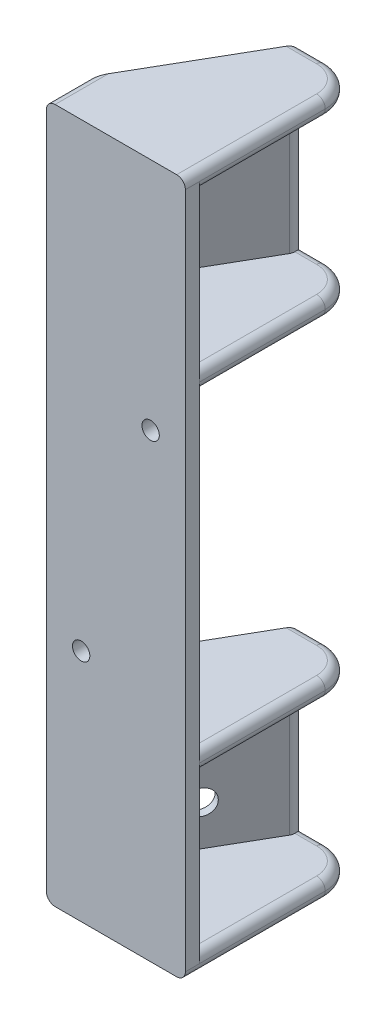
SolidWorks part; units mm, degrees
note: The reader was unsure of these and kept them because the rebuilt part matched: shared geometry of "Sketch2<2>".
material "ABS"
ref_plane "X-Y Datum" through (0, 0, 0) normal (0, 0, 1) x (1, 0, 0)
ref_plane "X-Z Datum" through (0, 0, 0) normal (0, 1, 0) x (1, 0, 0)
ref_plane "Y-Z Datum" through (0, 0, 0) normal (1, 0, 0) x (0, 0, -1)
sketch "Sketch1" plane through (0, 0, 0) normal (0, 1, 0) x (1, 0, 0)
  line L0 (0, 0) -> (-25.4, 0)
  line L1 (-25.4, 0) -> (-25.4, 6.985)
  line L2 (-25.4, 6.985) -> (0, 50.9791)
  line L3 (0, 50.9791) -> (0, 0)
  dimension "D1" = 25.4
  dimension "D2" = 60
  dimension "D3" = 6.985
extrude "Boss-Extrude1" add sketch "Sketch1" along normal blind 127
ref_plane "Plane1" through (0, 63.5, 0) normal (0, -1, 0) x (-1, 0, 0)
sketch "Sketch2" plane through (0, 63.5, 0) normal (0, -1, 0) x (-1, 0, 0)
  line L0 (0, 2.54) -> (23.8125, 2.54)
  line L1 (0, 0) -> (0, 50.9791) construction
  line L2 (23.8125, 2.54) -> (23.8125, 6.5596)
  line L3 (23.8125, 6.5596) -> (0, 47.8041)
  line L4 (0, 47.8041) -> (0, 2.54)
  line L5 (23.8125, 2.54) -> (23.8125, 0) construction
  line L6 (25.4, 0) -> (0, 0) construction
  line L7 (23.8125, 2.54) -> (25.4, 2.54) construction
  line L8 (25.4, 6.985) -> (25.4, 0) construction
  line L9 (25.4, 6.985) -> (24.0252, 6.1912) construction
  line L10 (0, 50.9791) -> (25.4, 6.985) construction
  dimension "D1" = 2.54
  dimension "D2" = 1.5875
extrude "Cut-Extrude1" cut sketch "Sketch2" against normal offset from surface (28.575 mm away) 3.175 from offset 31.75 up to face at (-12.7, 127, -14.491) offset against normal yes
extrude "Cut-Extrude2" cut sketch "Sketch2<2>" along normal offset from surface (28.575 mm away) 3.175 from offset 31.75 up to face at (-12.7, 0, -14.491)
sketch "Sketch2<2>" plane through (0, 63.5, 0) normal (0, -1, 0) x (-1, 0, 0) same geometry as "Sketch2"
sketch "Sketch3" plane through (0, 63.5, 0) normal (0, -1, 0) x (-1, 0, 0)
  line L0 (0, 0) -> (0, 50.9791) construction
  line L1 (25.4, 2.54) -> (0, 2.54)
  line L2 (25.4, 2.54) -> (25.4, 53.34)
  line L3 (25.4, 53.34) -> (0, 53.34)
  line L4 (0, 2.54) -> (0, 53.34)
  line L5 (25.4, 6.985) -> (25.4, 0) construction
  line L6 (23.8125, 2.54) -> (0, 2.54) construction
  dimension "D1" = 50.8
extrude "Cut-Extrude4" cut sketch "Sketch3" against normal mid plane 57.15
sketch "Sketch6" plane through (0, 0, 0) normal (0, -1, 0) x (1, 0, 0)
  line L0 (0, -31.9291) -> (0, -50.9791)
  line L1 (0, 0) -> (0, -50.9791) construction
  line L2 (0, -50.9791) -> (-10.9985, -31.9291)
  line L3 (0, -50.9791) -> (-25.4, -6.985) construction
  line L4 (-10.9985, -31.9291) -> (0, -31.9291)
  dimension "D1" = 19.05
extrude "Cut-Extrude7" cut sketch "Sketch6" against normal through all both and the other way through all
fillet "Fillet4" radius 6.35 4 edges at (0, 1.5875, -31.9291) (0, 33.3375, -31.9291) (0, 93.6625, -31.9291) (0, 125.4125, -31.9291)
fillet "Fillet2" radius 1.5875 30 edges at (0, 3.175, -14.0595) (0, 31.75, -14.0595) (0, 95.25, -14.0595) (0, 123.825, -14.0595) (-8.6743, 0, -31.9291) (-1.8599, 0, -30.0692) (-8.6743, 34.925, -31.9291) (-1.8599, 34.925, -30.0692) (-8.6743, 127, -31.9291) (-1.8599, 127, -30.0692) (-8.6743, 92.075, -31.9291) (-1.8599, 92.075, -30.0692) (-7.7577, 95.25, -31.9291) (-1.8599, 95.25, -30.0692) (-7.7577, 123.825, -31.9291) (-1.8599, 123.825, -30.0692) (-7.7577, 3.175, -31.9291) (-1.8599, 3.175, -30.0692) (-7.7577, 31.75, -31.9291) (-1.8599, 31.75, -30.0692) (-25.4, 127, -3.4925) (-25.4, 34.925, -4.7625) (-25.4, 92.075, -4.7625) (-25.4, 0, -3.4925) (0, 0, -12.7895) (0, 34.925, -14.0595) (0, 127, -12.7895) (0, 92.075, -14.0595) (-9.1654, 109.5375, -31.9291) (-9.1654, 17.4625, -31.9291)
sketch "Sketch4" plane through (-20.6998, 0, -11.951) normal (0.866, 0, 0.5) x (0.5, 0, -0.866)
  circle A0 centre (4.8771, 115.4668) radius 2.25
  circle A1 centre (8.5647, 10.5316) radius 2.25
  point P4 (0, 0)
  point P12 (0, 0)
  point P13 (0, 0)
  point P14 (0, 0)
  point P15 (0, 0)
  point P22 (0, 0)
  dimension "D1" = 4.5
  dimension "D2" = 8.5647
  dimension "D3" = 10.5316
  dimension "D4" = 104.9352
  dimension "D5" = 3.6877
extrude "Cut-Extrude5" cut sketch "Sketch4" against normal up to next
sketch "Sketch5" plane through (0, 0, -2.54) normal (0, 0, -1) x (-1, 0, 0)
  line L0 (0, 63.5) -> (25.4, 63.5) construction
  line L1 (6.35, 84.1375) -> (19.05, 84.1375) construction
  line L2 (6.35, 84.1375) -> (6.35, 42.8625) construction
  line L3 (6.35, 42.8625) -> (19.05, 42.8625) construction
  line L4 (19.05, 84.1375) -> (19.05, 42.8625) construction
  line L5 (6.35, 84.1375) -> (19.05, 42.8625) construction
  line L6 (6.35, 42.8625) -> (19.05, 84.1375) construction
  line L7 (0, 93.6625) -> (0, 33.3375) construction
  line L8 (25.4, 93.6625) -> (25.4, 33.3375) construction
  circle A0 centre (6.35, 84.1375) radius 1.5875
  circle A1 centre (19.05, 42.8625) radius 1.5875
  point P0 (12.7, 63.5)
  point P6 (12.7, 63.5)
  dimension "D3" = 3.175
  dimension "D1" = 12.7
  dimension "D2" = 41.275
extrude "Cut-Extrude6" cut sketch "Sketch5" against normal through all both and the other way through all
